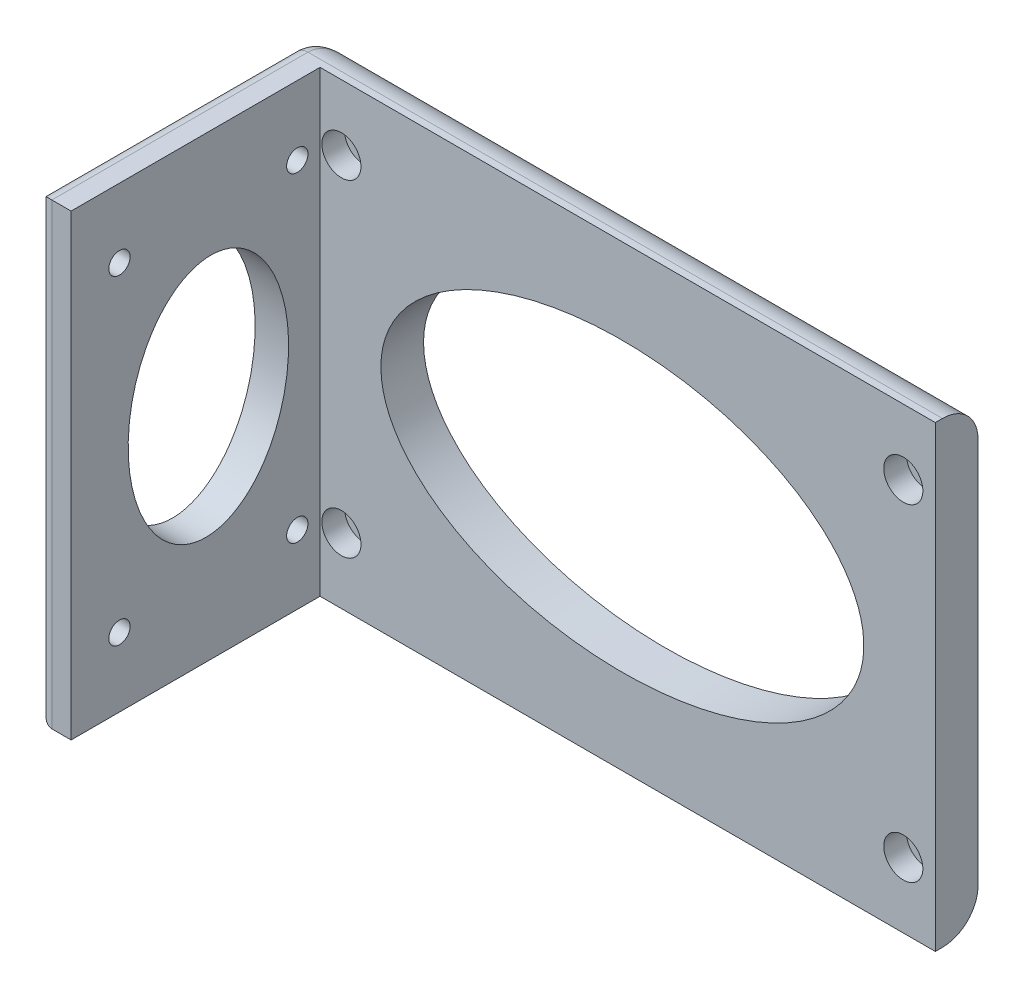
SolidWorks part; units mm, degrees
ref_plane "前视基准面" through (0, 0, 0) normal (0, 0, 1) x (1, 0, 0)
ref_plane "上视基准面" through (0, 0, 0) normal (0, 1, 0) x (1, 0, 0)
ref_plane "右视基准面" through (0, 0, 0) normal (1, 0, 0) x (0, 0, -1)
sketch "草图1" plane through (0, 0, 0) normal (0, 0, 1) x (1, 0, 0)
  line L5 (-44, -32.2) -> (44, -32.2)
  line L6 (-44, -32.2) -> (-44, 32.2)
  line L7 (-39.5, 23) -> (39.5, 23) construction
  line L8 (-39.5, 23) -> (-39.5, -23) construction
  line L9 (-39.5, -23) -> (39.5, -23) construction
  line L10 (39.5, 23) -> (39.5, -23) construction
  line L11 (-39.5, 23) -> (39.5, -23) construction
  line L12 (-39.5, -23) -> (39.5, 23) construction
  line L13 (-44, 32.2) -> (44, 32.2)
  line L14 (44, -32.2) -> (44, 32.2)
  line L15 (-44, -32.2) -> (44, 32.2) construction
  line L16 (-44, 32.2) -> (44, -32.2) construction
  circle A0 centre (-39.5, 23) radius 1.6
  circle A1 centre (39.5, 23) radius 1.6
  circle A2 centre (39.5, -23) radius 1.6
  circle A3 centre (-39.5, -23) radius 1.6
  point P0 (0, 0)
  point P4 (0, 0)
  point P6 (0, 0)
  dimension "D1" = 3.2
  dimension "D2" = 3.2
  dimension "D3" = 3.2
  dimension "D4" = 3.2
  dimension "D5" = 79
  dimension "D6" = 46
  dimension "D7" = 64.4
  dimension "D8" = 88
extrude "凸台-拉伸1" add sketch "草图1" along normal blind 6
sketch "草图2" plane through (0, 0, 6) normal (0, 0, 1) x (1, 0, 0)
  circle A0 centre (-39.5, 23) radius 2.75
  circle A1 centre (39.5, 23) radius 2.75
  circle A2 centre (-39.5, -23) radius 2.75
  circle A3 centre (39.5, -23) radius 2.75
  dimension "D1" = 5.5
  dimension "D2" = 5.5
  dimension "D3" = 5.5
  dimension "D4" = 5.5
extrude "切除-拉伸1" cut sketch "草图2" against normal blind 3.2
sketch "草图3" plane through (-44, 0, 0) normal (-1, 0, 0) x (0, 0, 1)
  line L0 (6, -32.2) -> (6, 32.2) construction
  line L1 (0, 32.2) -> (41, 32.2)
  line L2 (0, 32.2) -> (0, -32.2)
  line L3 (0, -32.2) -> (41, -32.2)
  line L4 (41, 32.2) -> (41, -32.2)
  line L5 (41, 0) -> (0, 0) construction
  line L6 (34.2, -22.5) -> (9.2, -22.5) construction
  line L7 (34.2, -22.5) -> (34.2, 22.5) construction
  line L8 (34.2, 22.5) -> (9.2, 22.5) construction
  line L9 (9.2, -22.5) -> (9.2, 22.5) construction
  line L10 (34.2, -22.5) -> (9.2, 22.5) construction
  line L11 (34.2, 22.5) -> (9.2, -22.5) construction
  circle A0 centre (34.2, -22.5) radius 1.5
  circle A1 centre (9.2, -22.5) radius 1.5
  circle A2 centre (34.2, 22.5) radius 1.5
  circle A3 centre (9.2, 22.5) radius 1.5
  point P13 (21.7, 0)
  dimension "D3" = 3
  dimension "D4" = 3
  dimension "D5" = 3
  dimension "D6" = 3
  dimension "D1" = 64.4
  dimension "D2" = 35
  dimension "D7" = 25
  dimension "D8" = 45
  dimension "D9" = 3.2
extrude "凸台-拉伸2" add sketch "草图3" along normal blind 3.2 and the other way blind 1.5
fillet "圆角1" radius 2 3 edges at (-47.2, 32.2, 20.5) (-47.2, 0, 41) (-47.2, -32.2, 20.5)
sketch "草图4" plane through (0, 0, 6) normal (0, 0, 1) x (1, 0, 0)
  ellipse E0 centre (0, 0) end of major axis (-33.9475, 0) minor radius 20.2178
extrude "切除-拉伸2" cut sketch "草图4" against normal blind 10
sketch "草图5" plane through (-42.5, 0, 0) normal (1, 0, 0) x (0, 0, -1)
  line L0 (0, 0) -> (-36.0079, 0) construction
  line L1 (-9.2, -22.5) -> (-34.2, -22.5) construction
  line L2 (-21.7, -22.5) -> (-21.7, 22.5) construction
  ellipse E0 centre (-21.7, 0) end of major axis (-21.0657, 16.9997) minor radius 11.2672
extrude "切除-拉伸3" cut sketch "草图5" against normal blind 10
fillet "圆角2" radius 5 5 edges at (-0.6, 32.2, 0) (-46.6142, 31.6142, 0) (-0.6, -32.2, 0) (-46.6142, -31.6142, 0) (-47.2, 0, 0)
